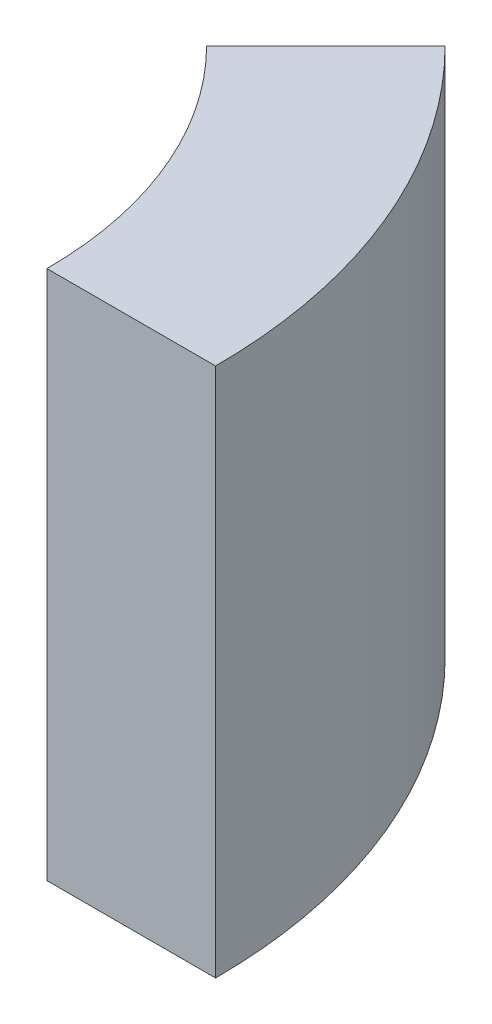
SolidWorks part; units mm, degrees
ref_plane "Front Plane" through (0, 0, 0) normal (0, 0, 1) x (1, 0, 0)
ref_plane "Top Plane" through (0, 0, 0) normal (0, 1, 0) x (1, 0, 0)
ref_plane "Right Plane" through (0, 0, 0) normal (1, 0, 0) x (0, 0, -1)
sketch "Sketch1" plane through (0, 0, 0) normal (0, 1, 0) x (1, 0, 0)
  line L0 (0, 0) -> (39.7333, 0) construction
  line L1 (11.3137, 11.3137) -> (16.2635, 16.2635)
  line L2 (16, 0) -> (23, 0)
  line L3 (14.7821, 6.1229) -> (0, 0) construction
  arc A0 (16, 0) -> (11.3137, 11.3137) centre (0, 0) ccw
  arc A1 (23, 0) -> (16.2635, 16.2635) centre (0, 0) ccw
  point P6 (14.7821, 6.1229)
  dimension "D1" = 16
  dimension "D3" = 23
  dimension "D4" = 7
  dimension "D2" = 45
  dimension "D5" = 22.5
extrude "Boss-Extrude1" add sketch "Sketch1" along normal blind 22
fillet "Fillet1" [suppressed] radius 0.4
sketch "Sketch2" plane through (0, 0, 0) normal (-0.7071, 0, -0.7071) x (-0.7071, 0, 0.7071)
  line L0 (-19.5, 5.2732) -> (-19.5, 21.6424) construction
  line L1 (-23, 22) -> (-23, 0) construction
  dimension "D1" = 3.5
sketch "Sketch3" plane through (0, 0, 0) normal (0, 0, 1) x (1, 0, 0)
  line L0 (19.5, 25.7921) -> (19.5, 3.555) construction
  line L1 (23, 22) -> (23, 0) construction
  dimension "D1" = 3.5
